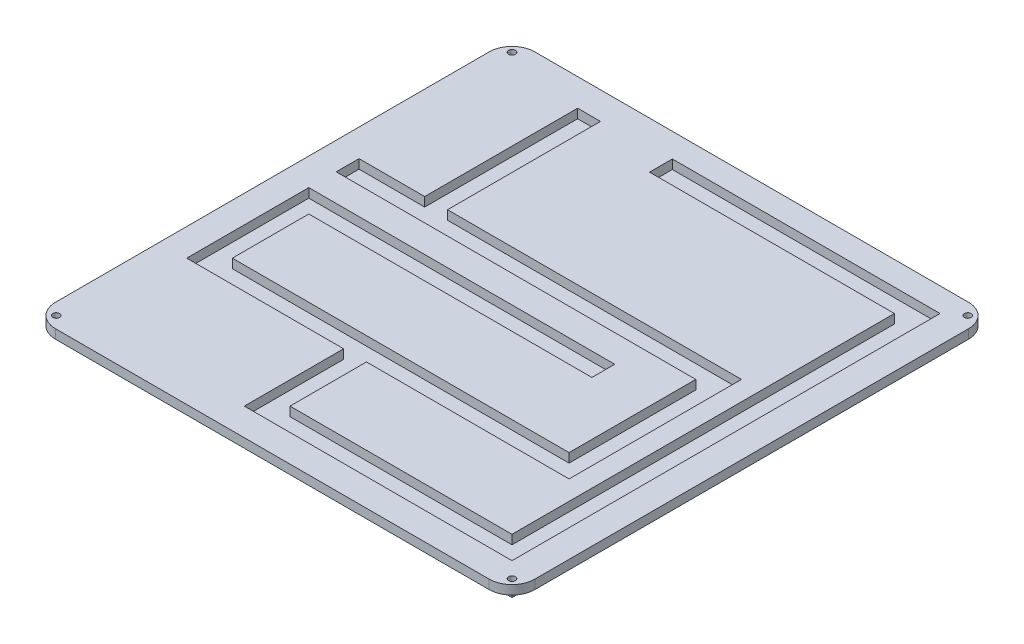
SolidWorks part; units mm, degrees
ref_plane "Front Plane" through (0, 0, 0) normal (0, 0, 1) x (1, 0, 0)
ref_plane "Top Plane" through (0, 0, 0) normal (0, 1, 0) x (1, 0, 0)
ref_plane "Right Plane" through (0, 0, 0) normal (1, 0, 0) x (0, 0, -1)
sketch "Sketch1" plane through (0, 0, 0) normal (0, 1, 0) x (1, 0, 0)
  line L0 (-101, -101) -> (-101, 101)
  line L5 (-105, -105) -> (105, -105)
  line L6 (-105, -105) -> (-105, 105)
  line L7 (-105, 105) -> (105, 105)
  line L8 (105, -105) -> (105, 105)
  line L9 (-101, 101) -> (101, 101)
  line L10 (101, -101) -> (101, 101)
  line L11 (-101, -101) -> (101, -101)
  line L12 (-101, 101) -> (-99.8333, 99.8333) construction
  line L13 (-55, 0) -> (55, 0) construction
  line L14 (-101, -101) -> (-99.8333, -99.8333) construction
  line L15 (0, -55) -> (0, 55) construction
  line L16 (101, -101) -> (99.8333, -99.8333) construction
  line L17 (101, 101) -> (99.8333, 99.8333) construction
  circle A1 centre (-99.8333, 99.8333) radius 1.5
  circle A2 centre (-99.8333, -99.8333) radius 1.5
  circle A3 centre (99.8333, -99.8333) radius 1.5
  circle A4 centre (99.8333, 99.8333) radius 1.5
  point P0 (0, 0)
  point P6 (-105, 0)
  point P7 (0, 105)
  dimension "D3" = 4
  dimension "D4" = 3
  dimension "D1" = 210
  dimension "D2" = 210
  dimension "D5" = 1.65
  dimension "D6" = 45
extrude "MainExtrude" add sketch "Sketch1" along normal blind 4 contours L6 L5 L8 L7
extrude "ScrewHoles" cut sketch "Sketch1<6>" along normal up to surface (4 mm away) contours A1 | A2 | A3 | A4 up to face at (0, 4, 0)
sketch "Sketch1<6>" plane through (0, 0, 0) normal (0, 1, 0) x (1, 0, 0) same geometry as "Sketch1"
fillet "RoundedCorners" radius 10 4 edges at (-105, 2, -105) (-105, 2, 105) (105, 2, -105) (105, 2, 105)
sketch "Sketch3" plane through (0, 0, 0) normal (0, 1, 0) x (1, 0, 0)
  line L24 (-59.25, 93) -> (-59.25, 26) construction
  line L25 (-64.25, 93) -> (-64.25, 26)
  line L58 (-93, 21) -> (69.5, 21) construction
  line L59 (69.5, 21) -> (69.5, -44.5) construction
  line L60 (69.5, -44.5) -> (-88, -44.5) construction
  line L61 (-88, -44.5) -> (-88, -1) construction
  line L62 (-88, -1) -> (41, -1) construction
  line L63 (-19.25, -49.5) -> (-19.25, -88) construction
  line L64 (-19.25, -88) -> (88, -88) construction
  line L65 (88, -88) -> (88, 89.5) construction
  line L66 (88, 89.5) -> (-24.25, 89.5) construction
  line L68 (-93, 16) -> (64.5, 16)
  line L69 (64.5, 16) -> (64.5, -39.5)
  line L70 (64.5, -39.5) -> (-83, -39.5)
  line L71 (-83, -39.5) -> (-83, -6)
  line L72 (-83, -6) -> (41, -6)
  line L73 (-24.25, -49.5) -> (-24.25, -93)
  line L74 (-24.25, -93) -> (93, -93)
  line L75 (93, -93) -> (93, 94.5)
  line L76 (93, 94.5) -> (-24.25, 94.5)
  line L77 (-54.25, 93) -> (-54.25, 26)
  line L78 (-93, 26) -> (-64.25, 26)
  line L79 (74.5, 26) -> (74.5, -49.5)
  line L80 (74.5, -49.5) -> (-14.25, -49.5)
  line L81 (-93, -49.5) -> (-93, 4)
  line L82 (-93, 4) -> (41, 4)
  line L83 (-14.25, -49.5) -> (-14.25, -83)
  line L84 (-14.25, -83) -> (83, -83)
  line L85 (83, -83) -> (83, 84.5)
  line L86 (83, 84.5) -> (-24.25, 84.5)
  line L87 (-64.25, 93) -> (-54.25, 93)
  line L89 (-93, 16) -> (-93, 26)
  line L90 (41, -6) -> (41, 4)
  line L92 (-24.25, 94.5) -> (-24.25, 84.5)
  line L93 (-54.25, 93) -> (-54.25, 39.3434) construction
  line L94 (-59.25, 93) -> (-59.25, 39.3434) construction
  line L95 (-64.25, 93) -> (-64.25, 39.3434) construction
  line L96 (-14.25, 9.5948) -> (-14.25, -83) construction
  line L97 (-19.25, 9.5948) -> (-19.25, -88) construction
  line L98 (-24.25, 9.5948) -> (-24.25, -93) construction
  line L99 (-24.25, -49.5) -> (-93, -49.5)
  line L100 (74.5, -49.5) -> (-93, -49.5) construction
  line L101 (-54.25, 26) -> (74.5, 26)
  line L102 (-93, 26) -> (74.5, 26) construction
  line L106 (-105, -95) -> (-105, 95) construction
  line L107 (-95, -105) -> (95, -105) construction
  line L108 (-95, 105) -> (95, 105) construction
  line L109 (105, -95) -> (105, 95) construction
  dimension "D1" = 5
  dimension "D2" = 5
  dimension "D3" = 12
  dimension "D4" = 12
  dimension "D5" = 12
  dimension "D6" = 12
  dimension "D7" = 67
  dimension "D8" = 167.5
  dimension "D9" = 134
  dimension "D11" = 117.25
  dimension "D13" = 33.5
  dimension "D14" = 117.25
  dimension "D10" = 33.5
  dimension "D12" = 167.5
  dimension "D15" = 30
  dimension "D17" = 167.5
  dimension "D16" = 55.5
extrude "Trench" cut sketch "Sketch3" along normal blind 12
extrude "Trench Walls" add sketch "Sketch3<7>" against normal blind 10 separate body
sketch "Sketch3<7>" plane through (0, 0, 0) normal (0, 1, 0) x (1, 0, 0) same geometry as "Sketch3"
